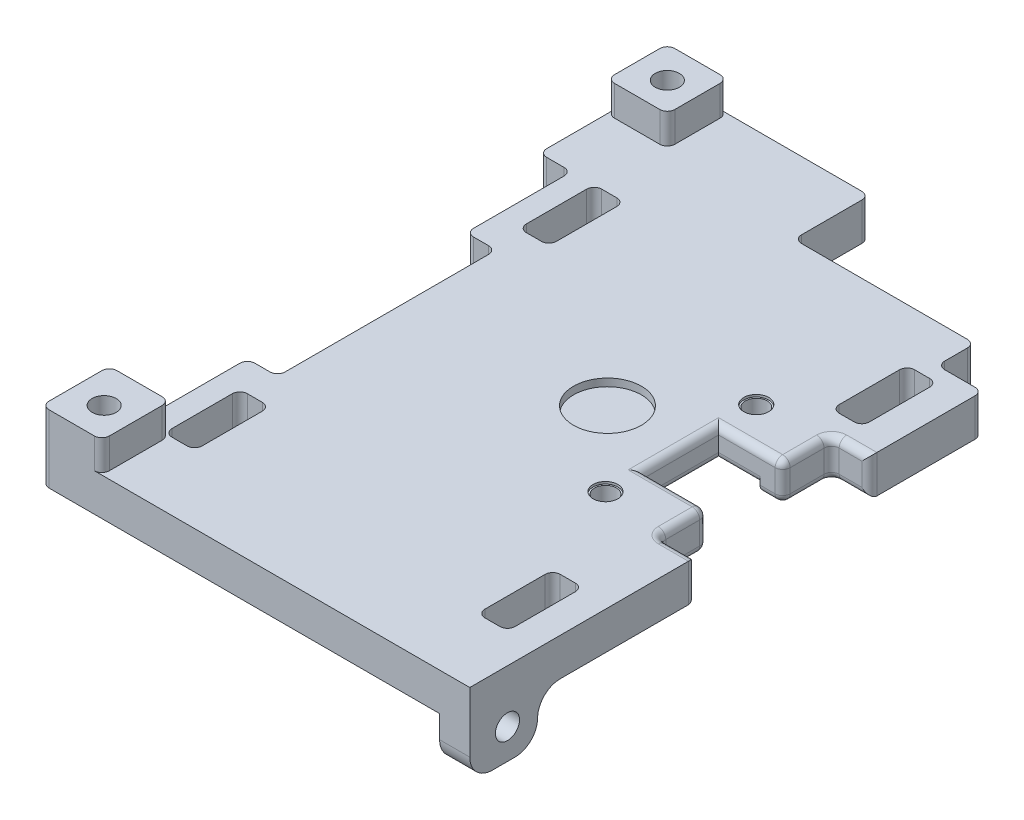
SolidWorks part; units mm, degrees
ref_plane "Front Plane" through (0, 0, 0) normal (0, 0, 1) x (1, 0, 0)
ref_plane "Top Plane" through (0, 0, 0) normal (0, 1, 0) x (1, 0, 0)
ref_plane "Right Plane" through (0, 0, 0) normal (1, 0, 0) x (0, 0, -1)
sketch "Sketch1" plane through (0, 0, 0) normal (0, 1, 0) x (1, 0, 0)
  line L1 (0, 0) -> (56.8, 0)
  line L2 (0, 0) -> (0, 83)
  line L3 (0, 83) -> (56.8, 83)
  line L4 (56.8, 0) -> (56.8, 83)
  dimension "D1" = 56.8
  dimension "D2" = 83
extrude "Main" add sketch "Sketch1" along normal blind 5
sketch "Vertical Mounts" plane through (0, 5, 0) normal (0, 1, 0) x (1, 0, 0)
  line L0 (4.15, 83) -> (4.15, 0) construction
  line L1 (56.8, 83) -> (0, 83) construction
  line L2 (0, 0) -> (56.8, 0) construction
  line L3 (0, 83) -> (0, 0) construction
  circle A0 centre (4.15, 78.85) radius 1.6
  circle A1 centre (4.15, 4.15) radius 1.6
  point P8 (4.15, 78.85)
  point P9 (4.15, 4.15)
  dimension "D4" = 3.2
  dimension "D1" = 4.15
  dimension "D2" = 4.15
  dimension "D3" = 4.15
extrude "Mount Vertical" cut sketch "Vertical Mounts" against normal up to next
sketch "Sketch3" plane through (0, 0, 0) normal (0, -1, 0) x (1, 0, 0)
  line L1 (56.8, 0) -> (52.8, 0)
  line L2 (56.8, 0) -> (56.8, -9)
  line L3 (56.8, -9) -> (52.8, -9)
  line L4 (52.8, 0) -> (52.8, -9)
  dimension "D1" = 4
  dimension "D2" = 9
extrude "Horizontal Mount " add sketch "Sketch3" along normal blind 6
sketch "Mount Horizontal" plane through (52.8, 0, 0) normal (-1, 0, 0) x (0, 0, 1)
  line L0 (-5, 0) -> (-5, -6) construction
  line L3 (0, -6) -> (0, 0) construction
  line L4 (-83, 0) -> (0, 0) construction
  line L5 (0, -6) -> (-9, -6) construction
  circle A0 centre (-5, -2) radius 1.6
  dimension "D1" = 3.2
  dimension "D2" = 2
  dimension "D3" = 5
fillet "Fillet1" radius 3 3 edges at (54.8, -6, 0) (54.8, -6, -9) (54.8, 0, -9)
extrude "Horizontal Hole" cut sketch "Mount Horizontal" against normal up to next
ref_plane "Plane1" through (0, 0, -41.5) normal (0, 0, 1) x (1, 0, 0)
sketch "Sketch5" plane through (0, 0, 0) normal (0, 1, 0) x (1, 0, 0)
  line L0 (48.8, 37.5) -> (56.8, 37.5) construction
  line L1 (11.3, 71) -> (48.8, 71)
  line L2 (11.3, 71) -> (11.3, 4)
  line L3 (11.3, 4) -> (48.8, 4)
  line L4 (48.8, 71) -> (48.8, 4)
  line L5 (56.8, 0) -> (56.8, 83) construction
  line L6 (30.05, 71) -> (30.05, 83) construction
  line L7 (56.8, 83) -> (0, 83) construction
  line L8 (30.05, 4) -> (30.05, 0) construction
  line L9 (0, 0) -> (52.8, 0) construction
  dimension "D1" = 67
  dimension "D2" = 37.5
  dimension "D3" = 8
  dimension "D4" = 12
extrude "Lip" cut sketch "Sketch5" along normal blind 1
sketch "Sketch6" plane through (0, 5, 0) normal (0, 1, 0) x (1, 0, 0)
  line L0 (30.05, 71) -> (30.05, 4) construction
  line L1 (48.8, 71) -> (11.3, 71) construction
  line L2 (11.3, 4) -> (48.8, 4) construction
  line L3 (11.3, 71) -> (11.3, 4) construction
  line L4 (11.3, 66) -> (7.3, 66)
  line L5 (11.3, 66) -> (11.3, 56)
  line L6 (11.3, 56) -> (7.3, 56)
  line L7 (7.3, 66) -> (7.3, 56)
  line L8 (11.3, 71) -> (11.3, 4) construction
  line L9 (11.3, 19) -> (7.3, 19)
  line L10 (11.3, 19) -> (11.3, 9)
  line L11 (11.3, 9) -> (7.3, 9)
  line L12 (7.3, 19) -> (7.3, 9)
  line L13 (48.8, 4) -> (48.8, 71) construction
  line L14 (48.8, 66) -> (52.8, 66)
  line L15 (48.8, 66) -> (48.8, 56)
  line L16 (48.8, 56) -> (52.8, 56)
  line L17 (52.8, 66) -> (52.8, 56)
  line L18 (48.8, 4) -> (48.8, 71) construction
  line L19 (48.8, 19) -> (52.8, 19)
  line L20 (48.8, 19) -> (48.8, 9)
  line L21 (48.8, 9) -> (52.8, 9)
  line L22 (52.8, 19) -> (52.8, 9)
  line L23 (11.3, 4) -> (48.8, 4) construction
  line L24 (48.8, 71) -> (11.3, 71) construction
  dimension "D1" = 5
  dimension "D2" = 10
  dimension "D3" = 5
  dimension "D4" = 4
extrude "Tie Downs" cut sketch "Sketch6" against normal up to next
sketch "Sketch7" plane through (0, 5, 0) normal (0, 1, 0) x (1, 0, 0)
  line L0 (0, 83) -> (0, 0) construction
  line L1 (4.3, 52) -> (8.3, 52)
  line L2 (0, 52) -> (0, 23)
  line L3 (4.3, 23) -> (8.3, 23)
  line L4 (8.3, 52) -> (8.3, 23)
  line L5 (0, 52) -> (8.3, 23) construction
  line L6 (0, 23) -> (8.3, 52) construction
  line L7 (11.3, 66) -> (7.3, 66) construction
  line L9 (0, 52) -> (0, 66)
  line L10 (0, 66) -> (4.3, 66)
  line L11 (4.3, 52) -> (4.3, 66)
  line L12 (0, 52) -> (4.3, 66) construction
  line L13 (0, 66) -> (4.3, 52) construction
  line L15 (0, 23) -> (0, 9)
  line L16 (0, 9) -> (4.3, 9)
  line L17 (4.3, 23) -> (4.3, 9)
  line L18 (0, 23) -> (4.3, 9) construction
  line L19 (0, 9) -> (4.3, 23) construction
  line L20 (7.3, 9) -> (11.3, 9) construction
  line L21 (11.3, 19) -> (7.3, 19) construction
  line L23 (7.3, 66) -> (7.3, 56) construction
  line L24 (11.3, 66) -> (11.3, 71) construction
  line L25 (0, 52) -> (4.3, 52) construction
  line L26 (0, 23) -> (4.3, 23) construction
  point P4 (4.15, 37.5)
  point P10 (2.15, 59)
  point P14 (2.15, 16)
  dimension "D1" = 4
  dimension "D2" = 3
  dimension "D3" = 3
extrude "Wire Clearance" cut sketch "Sketch7" against normal blind 10
fillet "Fillet2" radius 1 26 edges at (0, 2.5, 0) (0, 2.5, -83) (52.8, 2.5, -9) (48.8, 3, -9) (52.8, 2.5, -19) (48.8, 3, -19) (48.8, 3, -56) (52.8, 2.5, -56) (52.8, 2.5, -66) (48.8, 3, -66) (11.3, 3, -66) (11.3, 3, -56) (7.3, 2.5, -56) (7.3, 2.5, -66) (11.3, 3, -9) (7.3, 2.5, -9) (7.3, 2.5, -19) (11.3, 3, -19) (4.3, 2.5, -9) (0, 2.5, -9) (8.3, 2.5, -52) (0, 2.5, -66) (4.3, 2.5, -66) (4.3, 2.5, -52) (8.3, 2.5, -23) (4.3, 2.5, -23)
sketch "Sketch8" plane through (0, 0, 0) normal (0, -1, 0) x (1, 0, 0)
  line L0 (56.8, 0) -> (56.8, -83) construction
  line L4 (56.8, -30) -> (51.8, -30)
  line L5 (56.8, -30) -> (56.8, -53)
  line L6 (56.8, -53) -> (51.8, -53)
  line L7 (51.8, -30) -> (51.8, -53)
  line L8 (56.8, -30) -> (51.8, -53) construction
  line L9 (56.8, -53) -> (51.8, -30) construction
  line L10 (56.8, 0) -> (56.8, -83) construction
  line L11 (56.8, -41.5) -> (8.3, -41.5) construction
  line L12 (8.3, -51) -> (8.3, -24) construction
  point P10 (54.3, -41.5)
  dimension "D1" = 23
  dimension "D2" = 5
extrude "DF Charger Wire Pass Through" cut sketch "Sketch8" against normal up to next
sketch "Sketch9" plane through (0, 5, 0) normal (0, 1, 0) x (1, 0, 0)
  line L0 (56.8, 83) -> (56.8, 0) construction
  line L1 (56.8, 41.5) -> (43.3, 41.5) construction
  line L2 (43.3, 41.5) -> (43.3, 31.5) construction
  line L3 (43.3, 41.5) -> (43.3, 51.5) construction
  line L4 (56.8, 83) -> (1, 83) construction
  line L5 (1, 0) -> (56.8, 0) construction
  point P9 (43.3, 31.5)
  point P10 (43.3, 51.5)
  dimension "D1" = 13.5
  dimension "D2" = 20
hole_wizard "M2 Heat Sets" positions "3DSketch2" profile "Sketch11" counterbore size "M72" standard "ANSI Metric" end condition through all
sketch3d "3DSketch2"
  point P0 (43.3, 5, -31.5)
  point P3 (43.3, 5, -51.5)
sketch "Sketch11" plane through (43.3, 5, -31.5) normal (1, 0, 0) x (0, 0, 1)
  line L0 (0, 0) -> (0, 11)
  line L1 (0, 11) -> (1.45, 11)
  line L3 (1.45, 11) -> (1.45, 0.3)
  line L4 (1.45, 0.3) -> (1.65, 0.3)
  line L5 (1.65, 0.3) -> (1.65, 0)
  line L7 (1.65, 0) -> (0, 0)
  line L11 (0, -6.35) -> (0, 107.95) construction
  dimension "Thru Hole Dia." = 2.9
  dimension "Thru Hole Depth" = 11
  dimension "C'Bore Dia." = 3.3
  dimension "C'Bore Depth" = 0.3
sketch "Sketch12" plane through (0, 0, 0) normal (0, -1, 0) x (1, 0, 0)
  line L0 (48.8, -71) -> (11.3, -71) construction
  line L1 (56.8, -83) -> (26.8, -83)
  line L2 (56.8, -83) -> (56.8, -73)
  line L3 (50.8, -73) -> (26.8, -73)
  line L4 (26.8, -83) -> (26.8, -73)
  line L5 (56.8, -83) -> (26.8, -73) construction
  line L6 (56.8, -73) -> (26.8, -83) construction
  line L8 (56.8, -73) -> (50.8, -73) construction
  line L9 (56.8, -73) -> (56.8, -68)
  line L10 (56.8, -68) -> (50.8, -68)
  line L11 (50.8, -73) -> (50.8, -68)
  line L12 (56.8, -73) -> (50.8, -68) construction
  line L13 (56.8, -68) -> (50.8, -73) construction
  line L14 (51.8, -66) -> (48.8, -66) construction
  line L15 (56.8, -73) -> (50.8, -73) construction
  point P4 (41.8, -78)
  point P11 (53.8, -70.5)
  dimension "D1" = 2
  dimension "D2" = 30
  dimension "D3" = 6
  dimension "D4" = 2
extrude "Cut-Extrude2" cut sketch "Sketch12" against normal up to next
fillet "Fillet5" radius 1 15 edges at (51.8, 0, -41.5) (51.8, 5, -41.5) (54.3, 5, -30) (54.3, 0, -30) (54.3, 0, -53) (51.8, 2.5, -53) (54.3, 5, -53) (56.8, 2.5, -53) (51.8, 2.5, -30) (56.8, 2.5, -30) (26.8, 2.5, -83) (26.8, 2.5, -73) (56.8, 2.5, -68) (50.8, 2.5, -68) (50.8, 2.5, -73)
sketch "Sketch13" plane through (52.8, 0, 0) normal (-1, 0, 0) x (0, 0, 1)
  circle A0 centre (-5, -2) radius 3
  dimension "D1" = 6
extrude "Cut-Extrude3" cut sketch "Sketch13" along normal up to surface (4 mm away) up to face at (48.8, 0.5, -6.5)
fillet "Fillet6" radius 0.3 1 edges at (30.05, 0, -4)
sketch "Sketch15" plane through (0, 5, 0) normal (0, 1, 0) x (1, 0, 0)
  line L0 (0, 82) -> (0, 67) construction
  line L1 (25.8, 83) -> (1, 83) construction
  line L2 (0, 82) -> (0, 75)
  line L3 (8, 83) -> (1, 83)
  line L4 (0, 75) -> (8, 75)
  line L5 (8, 75) -> (8, 83)
  line L6 (1, 0) -> (56.8, 0) construction
  line L7 (0, 8) -> (0, 1) construction
  line L8 (1, 9) -> (3.3, 9) construction
  line L9 (1, 0) -> (8, 0)
  line L10 (0, 8) -> (0, 1)
  line L11 (1, 9) -> (3.3, 9)
  line L12 (3.3, 9) -> (8, 9)
  line L13 (8, 9) -> (8, 0)
  arc A0 (1, 83) -> (0, 82) centre (1, 82) ccw construction
  arc A1 (1, 83) -> (0, 82) centre (1, 82) ccw
  arc A2 (0, 1) -> (1, 0) centre (1, 1) ccw construction
  arc A3 (1, 9) -> (0, 8) centre (1, 8) ccw construction
  arc A4 (0, 1) -> (1, 0) centre (1, 1) ccw
  arc A5 (1, 9) -> (0, 8) centre (1, 8) ccw
  circle A6 centre (4.15, 4.15) radius 1.6 construction
  circle A7 centre (4.15, 78.85) radius 1.6 construction
  circle A8 centre (4.15, 4.15) radius 1.6
  circle A9 centre (4.15, 78.85) radius 1.6
  dimension "D1" = 8
  dimension "D2" = 8
extrude "Boss-Extrude1" add sketch "Sketch15" along normal blind 4
sketch "Sketch17" plane through (0, 5, 0) normal (0, 1, 0) x (1, 0, 0)
  line L0 (43.3, 51.5) -> (43.3, 31.5) construction
  line L1 (43.3, 41.5) -> (33.5654, 41.5) construction
  line L2 (43.3, 46.5) -> (55.3, 46.5)
  line L3 (43.3, 46.5) -> (43.3, 36.5)
  line L4 (43.3, 36.5) -> (55.3, 36.5)
  line L5 (55.3, 46.5) -> (55.3, 36.5)
  line L6 (43.3, 46.5) -> (55.3, 36.5) construction
  line L7 (43.3, 36.5) -> (55.3, 46.5) construction
  circle A0 centre (33.5654, 41.5) radius 4.5
  point P8 (49.3, 41.5)
  point P9 (43.3, 41.5)
  dimension "D3" = 9
  dimension "D1" = 10
  dimension "D2" = 12
extrude "Cut-Extrude4" cut sketch "Sketch17" against normal blind 1 contours A0
extrude "Cut-Extrude5" cut sketch "Sketch17<3>" against normal up to surface (5 mm away) and the other way through all contours L5 L2 L3 L4 region at (49.3, 5, -41.5) up to face at (4.15, 0, -80.45)
sketch "Sketch17<3>" plane through (0, 5, 0) normal (0, 1, 0) x (1, 0, 0) same geometry as "Sketch17"
fillet "Fillet7" radius 1 19 edges at (49.8, 0, -36.5) (51.5071, 0.2929, -36.5) (47.05, 5, -36.5) (51.5071, 4.7071, -36.5) (49.8, 0, -46.5) (51.5071, 0.2929, -46.5) (47.05, 5, -46.5) (51.5071, 4.7071, -46.5) (0, 7, -75) (8, 7, -83) (8, 7, -75) (8, 7, -9) (8, 7, 0) (43.3, 5, -41.5) (46.05, 1, -46.5) (46.05, 1, -36.5) (43.3, 1, -41.5) (51.8, 2.5, -36.5) (51.8, 2.5, -46.5)
